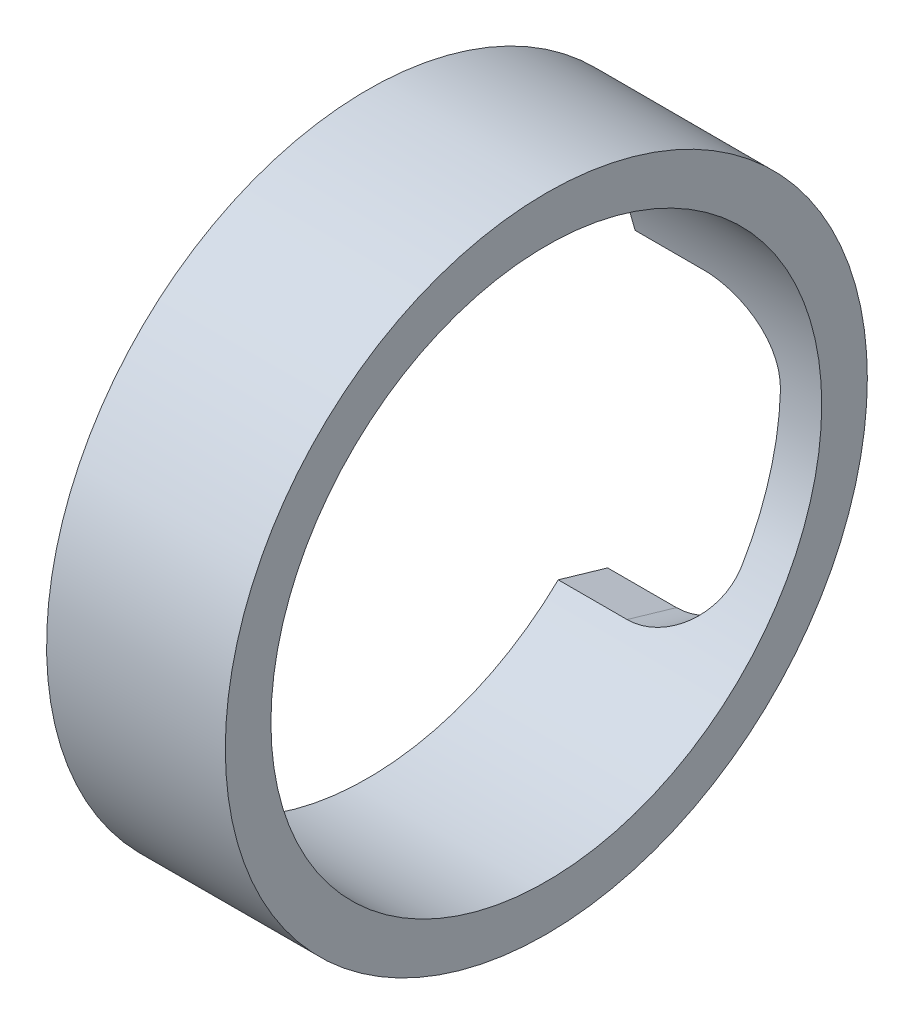
SolidWorks part; units mm, degrees
material "6061-T6 (SS)"
ref_plane "Front Plane" through (0, 0, 0) normal (0, 0, 1) x (1, 0, 0)
ref_plane "Top Plane" through (0, 0, 0) normal (0, 1, 0) x (1, 0, 0)
ref_plane "Right Plane" through (0, 0, 0) normal (1, 0, 0) x (0, 0, -1)
sketch "Sketch1" plane through (0, 0, 0) normal (0, 0, 1) x (1, 0, 0)
  line L1 (-39.3781, 8.89) -> (-34.4281, 8.89)
  line L2 (-39.3781, 8.89) -> (-39.3781, 7.627)
  line L3 (-39.3781, 7.627) -> (-34.4281, 7.627)
  line L4 (-34.4281, 8.89) -> (-34.4281, 7.627)
  line L7 (0, 0) -> (-47.1489, 0) construction
  line L8 (-39.3781, 10.4991) -> (-39.3781, 46.2794) construction
  line L9 (-34.4281, 15.2446) -> (-34.4281, -15.2446) construction
  dimension "D4" = 17.78
  dimension "D1" = 15.254
revolve "Revolve1" add sketch "Sketch1" angle 360 about L7
ref_plane "Plane1" through (0, -1.7465, -6.0042) normal (0, -0.2793, -0.9602) x (-1, 0, 0)
sketch "Sketch3" plane through (0, -1.7465, -6.0042) normal (0, -0.2793, -0.9602) x (-1, 0, 0)
  line L0 (39.3781, 3.81) -> (39.3781, -3.81)
  line L1 (39.3781, -7.627) -> (39.3781, 7.627) construction
  line L2 (39.3781, -3.81) -> (37.4731, -3.81)
  line L3 (35.5681, -1.905) -> (35.5681, 1.905)
  line L4 (37.4731, 3.81) -> (39.3781, 3.81)
  line L5 (39.3781, -8.89) -> (39.3781, 8.89) construction
  line L6 (39.3781, -8.89) -> (39.3781, 8.89) construction
  line L7 (35.5681, 0) -> (39.3781, 0) construction
  arc A2 (37.4731, -3.81) -> (35.5681, -1.905) centre (37.4731, -1.905) cw
  arc A3 (35.5681, 1.905) -> (37.4731, 3.81) centre (37.4731, 1.905) cw
  dimension "D1" = 7.62
  dimension "D2" = 3.81
extrude "Cut-Extrude1" cut sketch "Sketch3" along normal up to next
equation "\"D1@Sketch1\"=15mm+0.01in"
